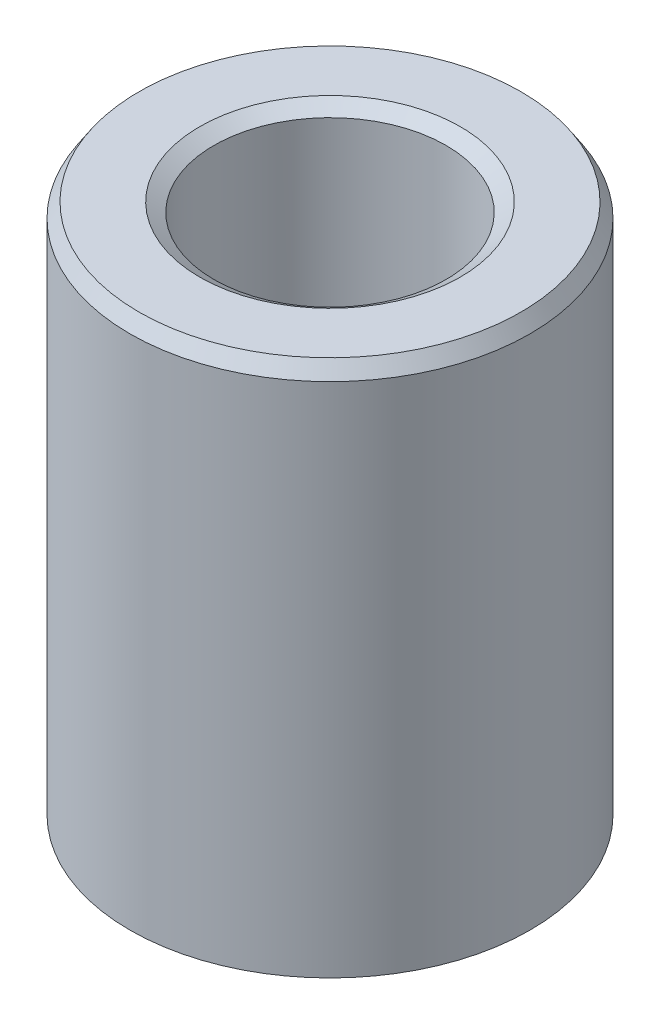
SolidWorks part; units mm, degrees
ref_plane "Front Plane" through (0, 0, 0) normal (0, 0, 1) x (1, 0, 0)
ref_plane "Top Plane" through (0, 0, 0) normal (0, 1, 0) x (1, 0, 0)
ref_plane "Right Plane" through (0, 0, 0) normal (1, 0, 0) x (0, 0, -1)
sketch "Sketch1" plane through (0, 0, 0) normal (0, 1, 0) x (1, 0, 0)
  circle A0 centre (0, 0) radius 47.5
  dimension "SLEEVE_OD" = 95
extrude "Boss-Extrude1" add sketch "Sketch1" along normal blind 128.1297
sketch "Sketch2" plane through (0, 0, 0) normal (0, 1, 0) x (1, 0, 0)
  circle A0 centre (0, 0) radius 27.5669
  dimension "BORE_D" = 55.1337
extrude "Cut-Extrude1" cut sketch "Sketch2" along normal through all
chamfer "Chamfer1" distance 3.3723 angle 32.814 4 edges at (0, 128.1297, 27.5669) (0, 0, 27.5669) (0, 0, 47.5) (0, 128.1297, 47.5) first distance on face at (0, 128.1297, 27.5669) first distance on face at (0, 0, 27.5669) first distance on face at (0, 128.1297, 47.5)
